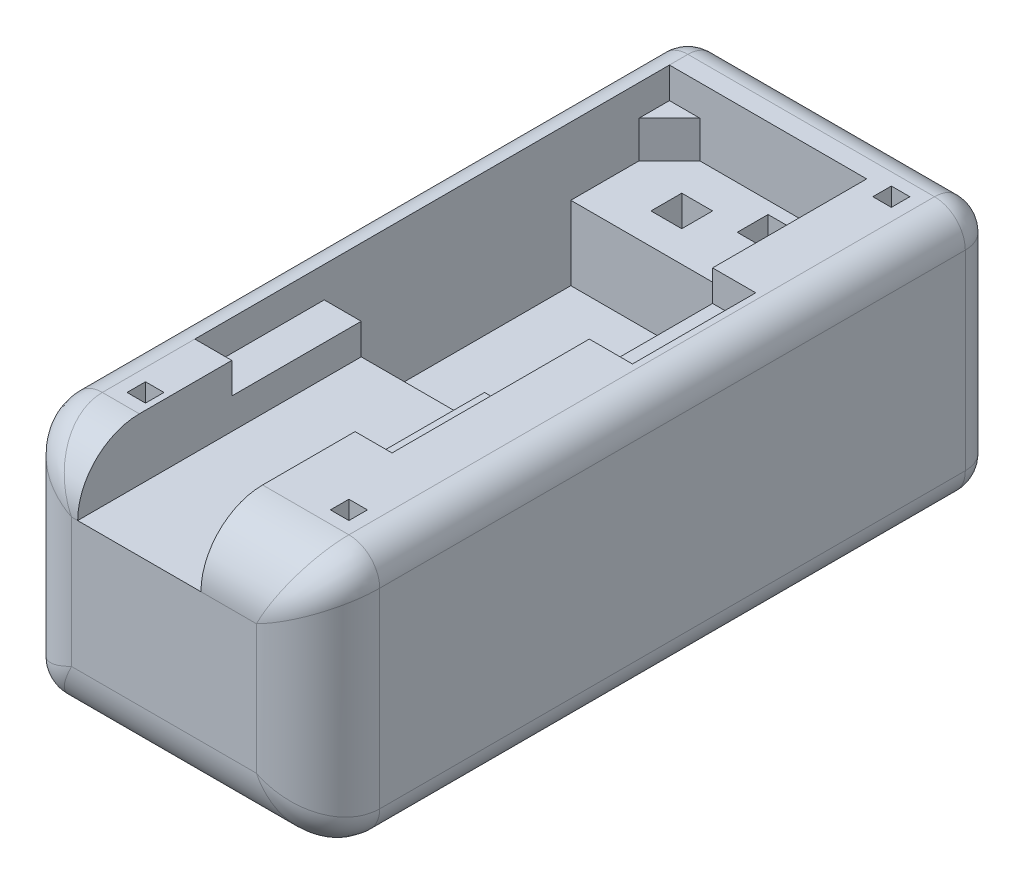
SolidWorks part; units mm, degrees
ref_plane "Front Plane" through (0, 0, 0) normal (0, 0, 1) x (1, 0, 0)
ref_plane "Top Plane" through (0, 0, 0) normal (0, 1, 0) x (1, 0, 0)
ref_plane "Right Plane" through (0, 0, 0) normal (1, 0, 0) x (0, 0, -1)
sketch "Sketch1" plane through (0, 0, 0) normal (0, 1, 0) x (1, 0, 0)
  line L0 (-45, 102) -> (-13, 102)
  line L1 (0, 0) -> (-50, 0)
  line L2 (0, 0) -> (0, 110)
  line L3 (0, 110) -> (-50, 110)
  line L4 (-50, 0) -> (-50, 110)
  line L5 (-13, 102) -> (-13, 77)
  line L6 (-13, 77) -> (-6, 77)
  line L7 (-6, 77) -> (-6, 57)
  line L8 (-6, 57) -> (-13, 57)
  line L9 (-13, 57) -> (-13, 25)
  line L10 (-13, 25) -> (-45, 25)
  line L11 (-45, 25) -> (-45, 102)
  dimension "D1" = 110
  dimension "D2" = 50
  dimension "D3" = 77
  dimension "D4" = 32
  dimension "D5" = 7
  dimension "D6" = 7
  dimension "D7" = 20
  dimension "D8" = 25
  dimension "D9" = 25
  dimension "D10" = 5
extrude "Boss-Extrude2" add sketch "Sketch1" along normal blind 40 contours L2 L3 L4 L1
extrude "Boss-Extrude5" add sketch "Sketch1<6>" along normal blind 3 from offset 38
sketch "Sketch1<6>" plane through (0, 0, 0) normal (0, 1, 0) x (1, 0, 0) same geometry as "Sketch1"
sketch "Sketch2" plane through (0, 40, 0) normal (0, 1, 0) x (1, 0, 0)
  line L0 (-45, 102) -> (-45, 25) construction
  line L1 (-45, 86) -> (-13, 86)
  line L2 (-45, 86) -> (-45, 46)
  line L3 (-45, 46) -> (-13, 46)
  line L4 (-13, 86) -> (-13, 46)
  line L5 (-13, 25) -> (-13, 57) construction
  line L6 (-13, 102) -> (-45, 102) construction
  dimension "D1" = 40
  dimension "D2" = 0
  dimension "D3" = 0
  dimension "D4" = 16
extrude "Cut-Extrude2" cut sketch "Sketch2" against normal blind 22 contours L2 L1 L4 L3
sketch "Sketch3" plane through (0, 40, 0) normal (0, 1, 0) x (1, 0, 0)
  line L0 (-13, 102) -> (-45, 102) construction
  line L1 (-37, 96) -> (-32, 96)
  line L2 (-37, 96) -> (-37, 91)
  line L3 (-37, 91) -> (-32, 91)
  line L4 (-32, 96) -> (-32, 91)
  line L6 (-13, 102) -> (-45, 102) construction
  line L7 (-13, 77) -> (-13, 102) construction
  line L9 (-27, 100) -> (-22, 100)
  line L10 (-27, 100) -> (-27, 95)
  line L11 (-27, 95) -> (-22, 95)
  line L12 (-22, 100) -> (-22, 95)
  line L13 (-45, 102) -> (-45, 25) construction
  line L14 (-45, 102) -> (-45, 86) construction
  dimension "D1" = 11
  dimension "D2" = 8
  dimension "D3" = 6
  dimension "D4" = 13
  dimension "D5" = 9
  dimension "D6" = 14
  dimension "D7" = 2
  dimension "D8" = 7
extrude "Cut-Extrude3" cut sketch "Sketch3" against normal through all contours L12 L9 L10 L11 | L2 L1 L4 L3 region at (-24.5, 40, -97.5)
sketch "Sketch4" plane through (0, 40, 0) normal (0, 1, 0) x (1, 0, 0)
  line L1 (-45, 102) -> (-13, 102)
  line L2 (-45, 102) -> (-45, 86)
  line L3 (-45, 86) -> (-13, 86)
  line L4 (-13, 102) -> (-13, 86)
extrude "Cut-Extrude4" cut sketch "Sketch4" against normal blind 10 contours L2 L1 L4 L3
sketch "Sketch5" plane through (0, 30, 0) normal (0, 1, 0) x (1, 0, 0)
  line L0 (-45, 102) -> (-40.0503, 102)
  line L1 (-45, 102) -> (-13, 102) construction
  line L2 (-40.0503, 102) -> (-45, 97.0503)
  line L3 (-45, 102) -> (-45, 86) construction
  line L4 (-45, 97.0503) -> (-45, 102)
  line L5 (-29, 102) -> (-29, 86)
  line L6 (-45, 86) -> (-13, 86) construction
  line L7 (-17.9497, 102) -> (-13, 97.0503)
  line L8 (-13, 102) -> (-17.9497, 102)
  line L9 (-13, 97.0503) -> (-13, 102)
  line M13 (-13, 86) -> (-13, 102)
  line M14 (-13, 102) -> (-45, 102)
  dimension "D1" = 45
  dimension "D2" = 7
extrude "Boss-Extrude7" add sketch "Sketch5" along normal blind 6 contours L7 M14 M13 | L4 L0 L2 region at (-14.6499, 30, -100.3501)
fillet "Fillet3" radius 5 8 edges at (0, 20.5, -110) (-50, 20.5, -110) (-25, 0, -110) (-50, 0, -55) (0, 0, -55) (0, 41, -55) (-25, 41, -110) (-50, 41, -55)
fillet "Fillet4" radius 10 8 edges at (-48.5355, 39.5355, 0) (-48.5355, 1.4645, 0) (-1.4645, 1.4645, 0) (-1.4645, 39.5355, 0) (0, 20.5, 0) (-50, 20.5, 0) (-25, 0, 0) (-25, 41, 0)
sketch "Sketch6" plane through (0, 41, 0) normal (0, 1, 0) x (1, 0, 0)
  line L0 (-13, 25) -> (-13, 57) construction
  line L1 (-39, 46) -> (-19, 46)
  line L2 (-39, 46) -> (-39, 0)
  line L3 (-39, 0) -> (-19, 0)
  line L4 (-19, 46) -> (-19, 0)
  line L5 (-45, 46) -> (-45, 25) construction
  line L6 (-10, 0) -> (-40, 0) construction
  line L8 (-45, 46) -> (-13, 46) construction
  dimension "D1" = 6
  dimension "D2" = 6
  dimension "D3" = 0
  dimension "D4" = 0
extrude "Cut-Extrude5" cut sketch "Sketch6" against normal blind 10 contours L2 L3 L4 L1
sketch "Sketch7" plane through (0, 41, 0) normal (0, 1, 0) x (1, 0, 0)
  line L0 (-5, 10) -> (-5, 105) construction
  line L1 (-10, 103) -> (-7, 103)
  line L2 (-10, 103) -> (-10, 100)
  line L3 (-10, 100) -> (-7, 100)
  line L4 (-7, 103) -> (-7, 100)
  line L5 (-5, 105) -> (-45, 105) construction
  line L6 (-45, 105) -> (-45, 102) construction
  line L7 (-43, 15) -> (-40, 15)
  line L8 (-43, 15) -> (-43, 12)
  line L9 (-43, 12) -> (-40, 12)
  line L10 (-40, 15) -> (-40, 12)
  line L11 (-45, 10) -> (-39, 10) construction
  line L12 (-19, 10) -> (-5, 10) construction
  line L13 (-10, 15) -> (-7, 15)
  line L14 (-10, 15) -> (-10, 12)
  line L15 (-10, 12) -> (-7, 12)
  line L16 (-7, 15) -> (-7, 12)
  dimension "D1" = 2
  dimension "D2" = 2
  dimension "D3" = 3
  dimension "D4" = 2
  dimension "D5" = 2
  dimension "D6" = 3
  dimension "D7" = 3
  dimension "D8" = 2
  dimension "D9" = 2
  dimension "D10" = 3
  dimension "D11" = 3
extrude "Cut-Extrude6" cut sketch "Sketch7" against normal blind 5
sketch "Sketch9" plane through (0, 40, 0) normal (0, 1, 0) x (1, 0, 0)
  line L1 (-39, 46) -> (-45, 46)
  line L2 (-39, 46) -> (-39, 25)
  line L3 (-39, 25) -> (-45, 25)
  line L4 (-45, 46) -> (-45, 25)
  line L5 (-13, 25) -> (-19, 25)
  line L6 (-13, 25) -> (-13, 46)
  line L7 (-13, 46) -> (-19, 46)
  line L8 (-19, 25) -> (-19, 46)
extrude "Cut-Extrude7" cut sketch "Sketch9" against normal blind 4
sketch "Sketch10" plane through (0, 40, 0) normal (0, 1, 0) x (1, 0, 0)
  line L1 (-6, 77) -> (-13, 77)
  line L2 (-6, 77) -> (-6, 57)
  line L3 (-6, 57) -> (-13, 57)
  line L4 (-13, 77) -> (-13, 57)
extrude "Cut-Extrude8" cut sketch "Sketch10" against normal blind 4 contours L2 L1 L4 L3
sketch "Sketch11" plane through (0, 41, 0) normal (0, 1, 0) x (1, 0, 0)
  line L0 (-10, 12) -> (-7, 12) construction
  line L1 (-45, 105) -> (-5, 105)
  line L2 (-45, 105) -> (-45, 10)
  line L3 (-45, 10) -> (-5, 10)
  line L4 (-5, 105) -> (-5, 10)
  line L5 (-7, 12) -> (-7, 15) construction
  line L8 (-13, 25) -> (-13, 57) construction
  dimension "D1" = 95
  dimension "D2" = 40
  dimension "D3" = 2
  dimension "D4" = 2
  dimension "D5" = 8
